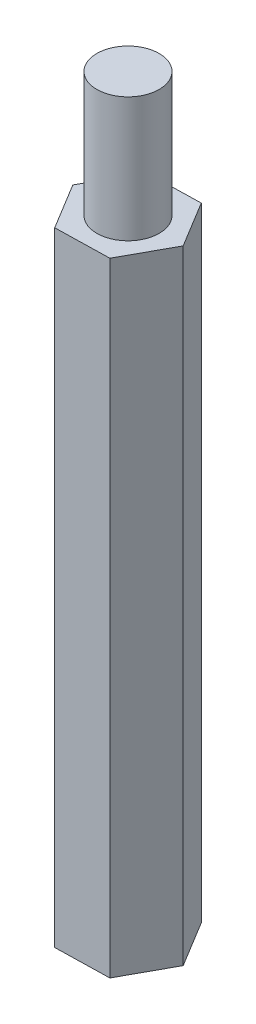
SolidWorks part; units mm, degrees
ref_plane "前视基准面" through (0, 0, 0) normal (0, 0, 1) x (1, 0, 0)
ref_plane "上视基准面" through (0, 0, 0) normal (0, 1, 0) x (1, 0, 0)
ref_plane "右视基准面" through (0, 0, 0) normal (1, 0, 0) x (0, 0, -1)
sketch "草图1" plane through (0, 0, 0) normal (0, 1, 0) x (1, 0, 0)
  line L1 (1.2485, 2.2784) -> (-1.349, 2.2204)
  line L2 (-1.349, 2.2204) -> (-2.5974, -0.058)
  line L3 (-2.5974, -0.058) -> (-1.2485, -2.2784)
  line L4 (-1.2485, -2.2784) -> (1.349, -2.2204)
  line L5 (1.349, -2.2204) -> (2.5974, 0.058)
  line L6 (2.5974, 0.058) -> (1.2485, 2.2784)
  circle A0 centre (0, 0) radius 2.25 construction
  circle A1 centre (0, 0) radius 1.5
  dimension "D2" = 3
  dimension "D1" = 4.5
extrude "凸台-拉伸1" add sketch "草图1" along normal blind 30
extrude "凸台-拉伸2" add sketch "草图1<2>" along normal blind 36 contours A1 region at (0, 0, 0)
sketch "草图1<2>" plane through (0, 0, 0) normal (0, 1, 0) x (1, 0, 0) same geometry as "草图1"
cosmetic thread "装饰螺纹线1" parameters "D2"=2.459
sketch "草图2" plane through (0, 0, 0) normal (0, -1, 0) x (1, 0, 0)
  circle A0 centre (0, 0) radius 1.5
  dimension "D1" = 3
extrude "切除-拉伸1" cut sketch "草图2" against normal blind 8
cosmetic thread "装饰螺纹线2" parameters "D2"=4
